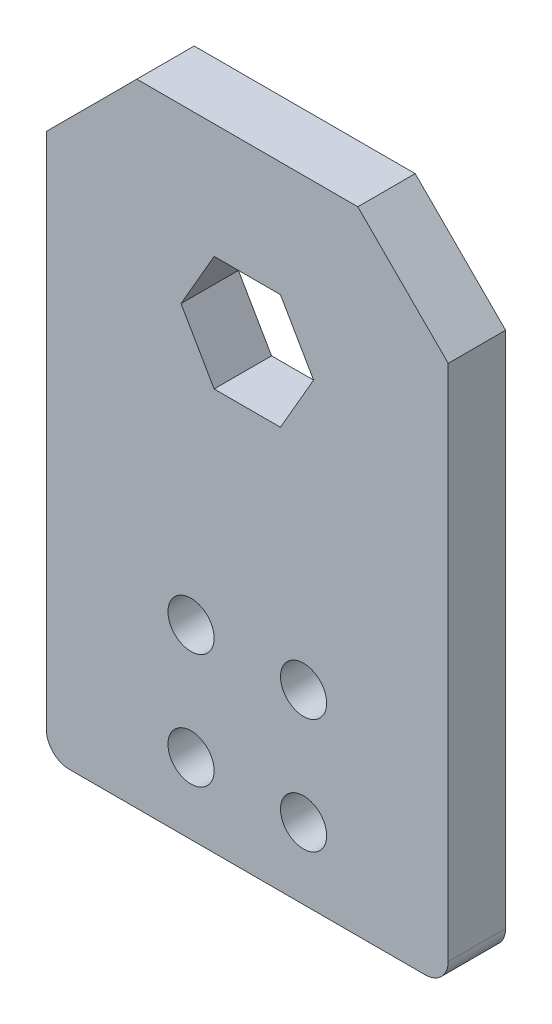
SolidWorks part; units mm, degrees
material "5052-O"
ref_plane "Front Plane" through (0, 0, 0) normal (0, 0, 1) x (1, 0, 0)
ref_plane "Top Plane" through (0, 0, 0) normal (0, 1, 0) x (1, 0, 0)
ref_plane "Right Plane" through (0, 0, 0) normal (1, 0, 0) x (0, 0, -1)
sketch "Sketch1" plane through (0, 0, 0) normal (0, 0, 1) x (1, 0, 0)
  line L1 (-22.225, -34.925) -> (22.225, -34.925)
  line L2 (-22.225, -34.925) -> (-22.225, 34.925)
  line L3 (-22.225, 34.925) -> (22.225, 34.925)
  line L4 (22.225, -34.925) -> (22.225, 34.925)
  line L5 (-22.225, -34.925) -> (22.225, 34.925) construction
  line L6 (-22.225, 34.925) -> (22.225, -34.925) construction
  point P0 (0, 0)
  dimension "D1" = 44.45
  dimension "D2" = 69.85
extrude "Boss-Extrude1" add sketch "Sketch1" along normal mid plane 6.35
chamfer "Chamfer1" distance 10 angle 45 2 edges at (22.225, 34.925, 0) (-22.225, 34.925, 0)
sketch "Sketch2" plane through (0, 0, 3.175) normal (0, 0, 1) x (1, 0, 0)
  line L1 (12.225, 34.925) -> (-12.225, 34.925) construction
  line L2 (7.3323, 15.875) -> (3.6662, 22.225)
  line L3 (3.6662, 22.225) -> (-3.6662, 22.225)
  line L4 (-3.6662, 22.225) -> (-7.3323, 15.875)
  line L5 (-7.3323, 15.875) -> (-3.6662, 9.525)
  line L6 (-3.6662, 9.525) -> (3.6662, 9.525)
  line L7 (3.6662, 9.525) -> (7.3323, 15.875)
  circle A1 centre (0, 15.875) radius 6.35 construction
  dimension "D1" = 19.05
  dimension "D2" = 12.7
extrude "Cut-Extrude1" cut sketch "Sketch2" against normal through all
hole_wizard "Tap Drill for #10-24 Tap1" positions "Sketch4" profile "Sketch5" hole size "#10-24" standard "ANSI Inch"
sketch "Sketch4" plane through (0, -34.925, 0) normal (0, -1, 0) x (-1, 0, 0)
  line L0 (15.875, 0) -> (-15.875, 0) construction
  point P0 (15.875, 0)
  point P2 (-15.875, 0)
  point P13 (0, 0)
  dimension "D1" = 31.75
sketch "Sketch5" plane through (-15.875, -34.925, 0) normal (1, 0, 0) x (0, 0, -1)
  line L0 (0, 0) -> (0, 20.1908)
  line L1 (0, 20.1908) -> (1.8986, 19.05)
  line L2 (1.8986, 19.05) -> (1.8986, 0)
  line L5 (1.8986, 0) -> (0, 0)
  line L10 (0, 20.1908) -> (-1.8987, 19.05) construction
  line L11 (0, -6.35) -> (0, 107.95) construction
  dimension "Hole Dia." = 3.7973
  dimension "Hole Depth" = 19.05
  dimension "Drill Angle" = 118
sketch "Sketch6" plane through (0, 0, 3.175) normal (0, 0, 1) x (1, 0, 0)
  line L0 (-22.225, -34.925) -> (22.225, -34.925) construction
  line L1 (-6.223, -27.051) -> (6.223, -27.051) construction
  line L2 (-6.223, -27.051) -> (-6.223, -14.351) construction
  line L3 (-6.223, -14.351) -> (6.223, -14.351) construction
  line L4 (6.223, -27.051) -> (6.223, -14.351) construction
  line L5 (-6.223, -27.051) -> (6.223, -14.351) construction
  line L6 (-6.223, -14.351) -> (6.223, -27.051) construction
  point P0 (0, -20.701)
  dimension "D1" = 7.874
  dimension "D2" = 12.446
  dimension "D3" = 12.7
hole_wizard "#10 Clearance Hole1" positions "Sketch7" profile "Sketch8" hole size "#10" standard "ANSI Inch"
sketch "Sketch7" plane through (0, 0, 3.175) normal (0, 0, 1) x (1, 0, 0)
  point P0 (-6.223, -14.351)
  point P3 (6.223, -14.351)
  point P6 (6.223, -27.051)
  point P9 (-6.223, -27.051)
sketch "Sketch8" plane through (-6.223, -14.351, 3.175) normal (1, 0, 0) x (0, -1, 0)
  line L0 (0, 0) -> (0, 14.2338)
  line L1 (0, 14.2338) -> (2.5527, 12.7)
  line L2 (2.5527, 12.7) -> (2.5527, 0)
  line L5 (2.5527, 0) -> (0, 0)
  line L10 (0, 14.2338) -> (-2.5527, 12.7) construction
  line L11 (0, -6.35) -> (0, 107.95) construction
  dimension "Hole Dia." = 5.1054
  dimension "Hole Depth" = 12.7
  dimension "Drill Angle" = 118
fillet "Fillet1" radius 2.54 2 edges at (22.225, -34.925, 0) (-22.225, -34.925, 0)
ref_axis "Axis1" through (0, 15.875, 3.175) along (0, 0, 1)
